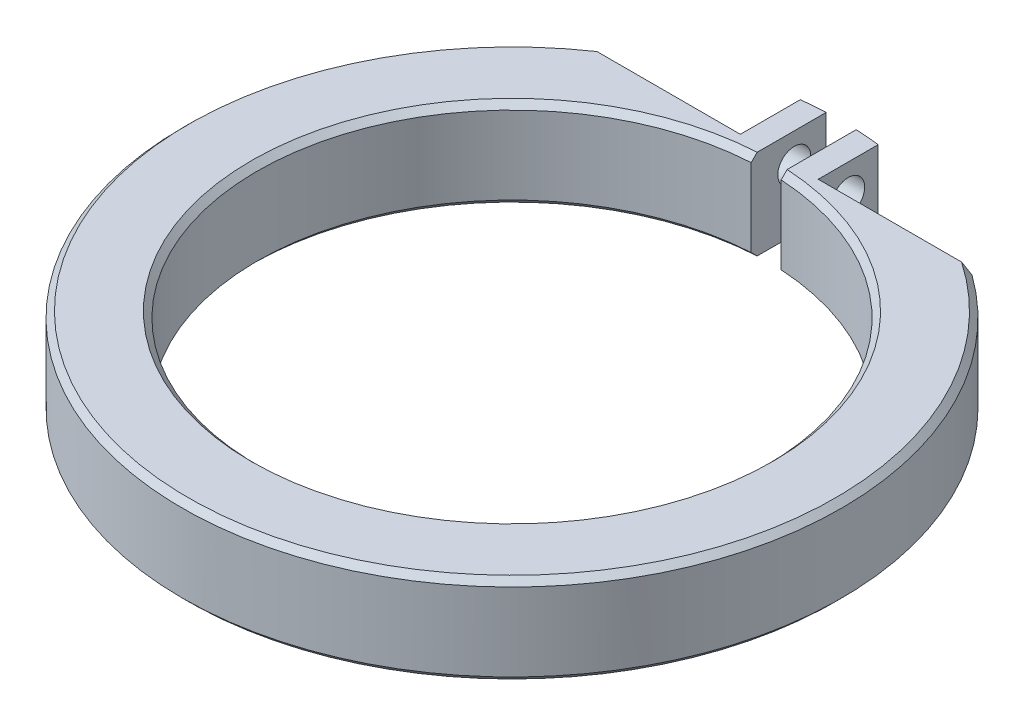
SolidWorks part; units mm, degrees
material "1.0037 (S235JR)"
ref_plane "Front Plane" through (0, 0, 0) normal (0, 0, 1) x (1, 0, 0)
ref_plane "Top Plane" through (0, 0, 0) normal (0, 1, 0) x (1, 0, 0)
ref_plane "Right Plane" through (0, 0, 0) normal (1, 0, 0) x (0, 0, -1)
sketch "Sketch1" plane through (0, 0, 0) normal (0, 1, 0) x (1, 0, 0)
  circle A0 centre (0, 0) radius 42.5
  circle A1 centre (0, 0) radius 55
  dimension "D1" = 85
  dimension "D2" = 110
extrude "Boss-Extrude1" add sketch "Sketch1" along normal blind 15
sketch "Sketch2" plane through (0, 15, 0) normal (0, 1, 0) x (1, 0, 0)
  line L0 (0, -1000) -> (0, 49000) construction
  line L1 (-2.5, 42.4264) -> (-2.5, 54.9432)
  line L2 (2.5, 42.4264) -> (2.5, 54.9432)
  circle A0 centre (0, 0) radius 42.5 construction
  circle A1 centre (0, 0) radius 55 construction
  arc A2 (2.5, 42.4264) -> (-2.5, 42.4264) centre (0, 0) ccw
  arc A3 (2.5, 54.9432) -> (-2.5, 54.9432) centre (0, 0) ccw
  dimension "D1" = 5
extrude "Cut-Extrude1" cut sketch "Sketch2" against normal through all
sketch "Sketch3" plane through (0, 15, 0) normal (0, 1, 0) x (1, 0, 0)
  line L0 (-6.5, 54.6146) -> (-6.5, 44.6146)
  line L1 (-6.5, 44.6146) -> (-32.1643, 44.6146)
  line L3 (-2.5, 54.9432) -> (-2.5, 42.4264) construction
  line L4 (0, -1000) -> (0, 49000) construction
  line L5 (6.5, 44.6146) -> (32.1643, 44.6146)
  line L6 (6.5, 54.6146) -> (6.5, 44.6146)
  arc A0 (-2.5, 54.9432) -> (2.5, 54.9432) centre (0, 0) ccw construction
  arc A1 (-6.5, 54.6146) -> (-32.1643, 44.6146) centre (0, 0) ccw
  arc A3 (6.5, 54.6146) -> (32.1643, 44.6146) centre (0, 0) cw
  dimension "D1" = 10
  dimension "D2" = 4
extrude "Cut-Extrude2" cut sketch "Sketch3" against normal blind 10
sketch "Sketch4" plane through (-6.5, 0, 0) normal (-1, 0, 0) x (0, 0, 1)
  line L0 (-44.6146, 15) -> (-54.6146, 15) construction
  line L1 (-54.6146, 5) -> (-54.6146, 15) construction
  circle A0 centre (-49.6146, 10) radius 2.75
  point P2 (-49.6146, 15)
  point P6 (-54.6146, 10)
  dimension "D1" = 5.5
extrude "Cut-Extrude3" cut sketch "Sketch4" against normal through all
fillet "Fillet2" radius 2 2 edges at (-19.3321, 5, -44.6146) (19.3321, 5, -44.6146)
chamfer "Chamfer2" distance 1 angle 45 2 edges at (0, 15, 55) (0, 0, 55)
chamfer "Chamfer3" distance 1 angle 45 2 edges at (0, 0, 42.5) (0, 15, 42.5)
